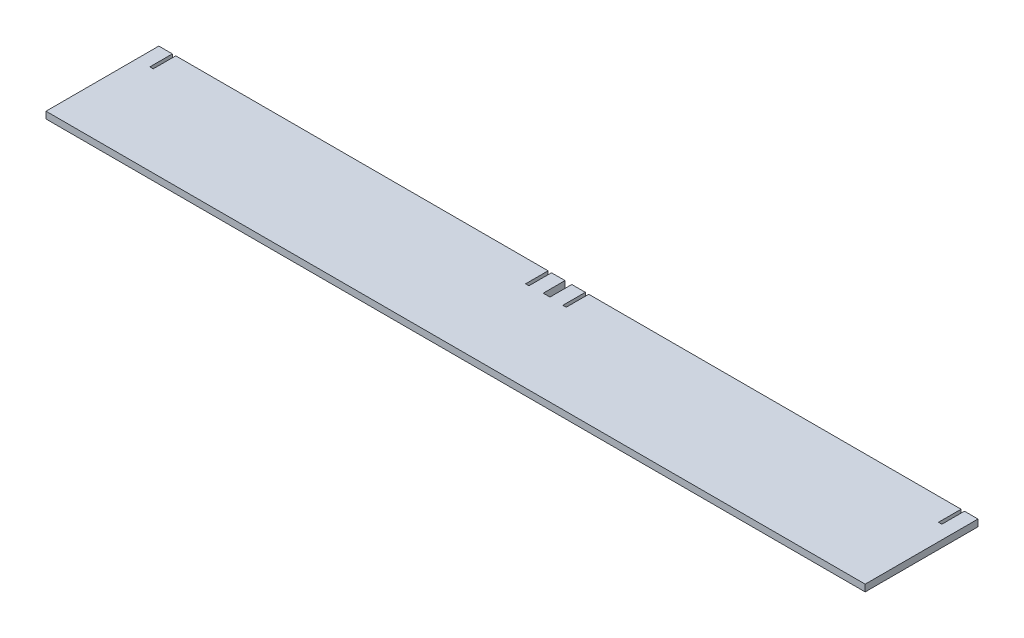
SolidWorks part; units mm, degrees
ref_plane "Front Plane" through (0, 0, 0) normal (0, 0, 1) x (1, 0, 0)
ref_plane "Top Plane" through (0, 0, 0) normal (0, 1, 0) x (1, 0, 0)
ref_plane "Right Plane" through (0, 0, 0) normal (1, 0, 0) x (0, 0, -1)
sketch "Sketch1" plane through (0, 0, 0) normal (0, 1, 0) x (1, 0, 0)
  line L0 (-84, 25) -> (-84, 15)
  line L1 (-90, -25) -> (90, -25)
  line L2 (-90, -25) -> (-90, 25)
  line L3 (-90, 25) -> (-84, 25)
  line L4 (90, -25) -> (90, 25)
  line L5 (-84, 15) -> (-82.5, 15)
  line L6 (-82.5, 15) -> (-82.5, 25)
  line L7 (82.5, 25) -> (82.5, 15)
  line L8 (82.5, 15) -> (84, 15)
  line L9 (84, 15) -> (84, 25)
  line L10 (-82.5, 25) -> (82.5, 25)
  line L11 (84, 25) -> (90, 25)
  point P4 (-90, 0)
  point P5 (0, 25)
  dimension "D1" = 50
  dimension "D2" = 180
  dimension "D3" = 6
  dimension "D4" = 1.5
  dimension "D5" = 10
extrude "Boss-Extrude1" add sketch "Sketch1" along normal mid plane 3
sketch "Sketch2" plane through (0, 0, 0) normal (0, 1, 0) x (1, 0, 0)
  line L0 (90, -25) -> (90, 25) construction
  line L1 (90, 15.3314) -> (93, 15.3314)
  line L2 (90, 15.3314) -> (90, -25)
  line L3 (90, -25) -> (93, -25)
  line L4 (93, 15.3314) -> (93, -25)
  line L5 (-90, -25) -> (90, -25) construction
  dimension "D1" = 3
extrude "Boss-Extrude2" add sketch "Sketch2" along normal mid plane 3
pattern_linear "LPattern2" count 2 spacing 183 along (1, 0, 0) of "Boss-Extrude1"
equation "\"mdfWidth\"= 3"
equation "\"cellSide\"= 180"
equation "\"mazeHeight\" = 50"
equation "\"slitHeight\"= 10"
equation "\"slitWidth\" = \"wallThickness\""
equation "\"gripWidth\"= 6"
equation "\"wallThickness\"= 1.5"
equation "\"D1@Sketch1\"= \"mazeHeight\""
equation "\"D2@Sketch1\"= \"cellSide\""
equation "\"D3@Sketch1\"= \"gripWidth\""
equation "\"D4@Sketch1\"= \"wallThickness\""
equation "\"D5@Sketch1\"= \"slitHeight\""
equation "\"D1@Boss-Extrude1\"= \"mdfWidth\""
equation "\"D1@Sketch2\"= \"mdfWidth\""
equation "\"D1@Boss-Extrude2\"= \"mdfWidth\""
equation "\"D1@LPattern1\"= 2"
equation "\"D3@LPattern1\"= \"cellSide\" + \"mdfWidth\""
equation "\"nbUnits\"= 2"
equation "\"D1@LPattern2\"= \"nbUnits\""
